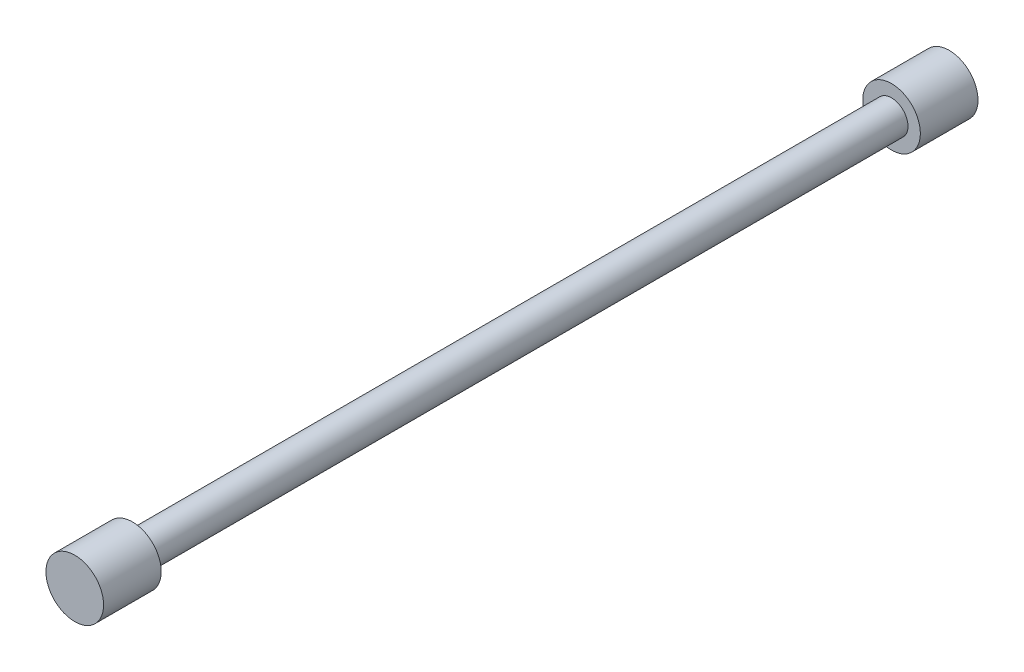
SolidWorks part; units mm, degrees
ref_plane "Front Plane" through (0, 0, 0) normal (0, 0, 1) x (1, 0, 0)
ref_plane "Top Plane" through (0, 0, 0) normal (0, 1, 0) x (1, 0, 0)
ref_plane "Right Plane" through (0, 0, 0) normal (1, 0, 0) x (0, 0, -1)
sketch "SK_Rod" plane through (0, 0, 0) normal (0, 1, 0) x (1, 0, 0)
  line L0 (0, -10) -> (0, 208.3633) construction
  line L1 (0, -7) -> (7, -7)
  line L2 (7, -7) -> (7, 7)
  line L3 (7, 7) -> (4, 7)
  line L4 (4, 7) -> (4, 191.3633)
  line L5 (4, 191.3633) -> (7, 191.3633)
  line L6 (7, 191.3633) -> (7, 205.3633)
  line L7 (7, 205.3633) -> (0, 205.3633)
  line L8 (0, 205.3633) -> (0, -7)
  dimension "P1" = 10
  dimension "P2" = 208.3633
  dimension "P3" = 7
  dimension "P4" = 7
  dimension "P5" = 7
  dimension "P6" = 7
  dimension "P7" = 7
  dimension "P8" = 4
  dimension "P9" = 7
  dimension "P10" = 4
  dimension "P11" = 191.3633
  dimension "P12" = 7
  dimension "P13" = 191.3633
  dimension "P14" = 7
  dimension "P15" = 205.3633
  dimension "P16" = 205.3633
revolve "Rod_Body" add sketch "SK_Rod" angle 360 about L0
equation "\"Rod_length\" = 198.363"
